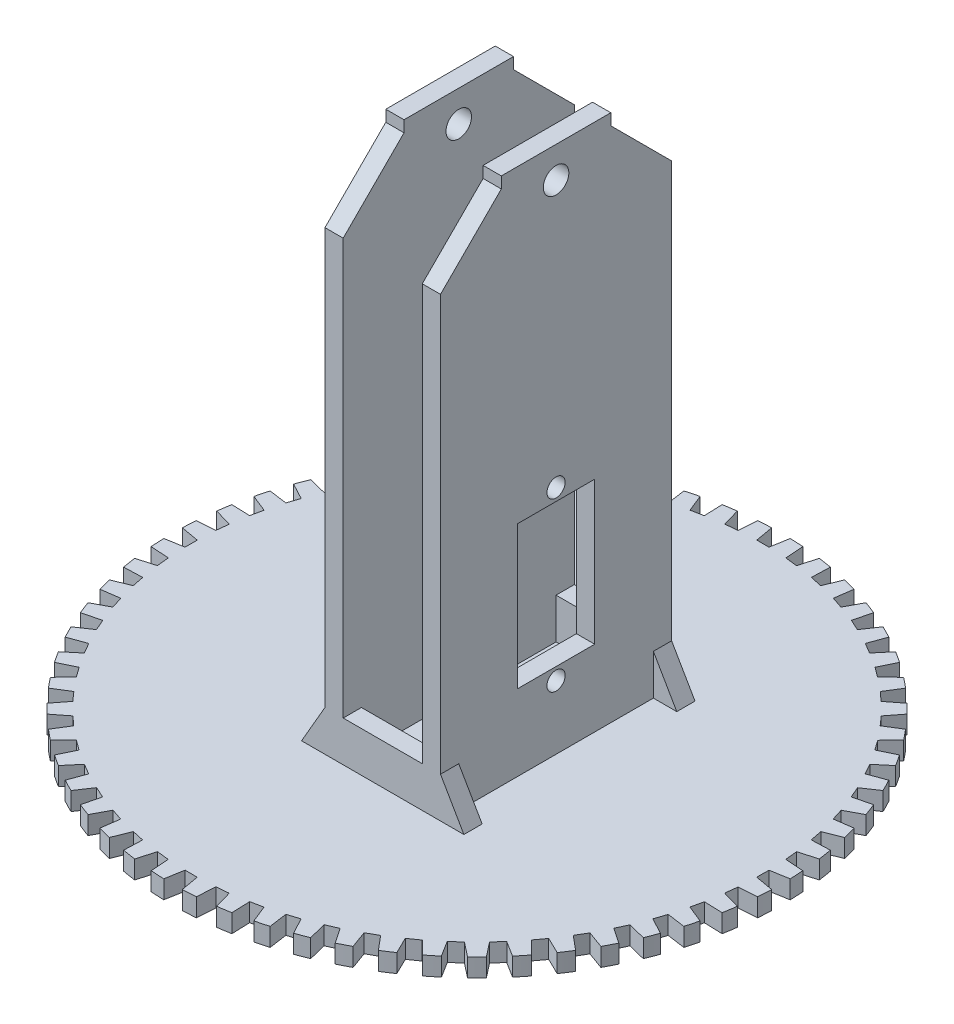
SolidWorks part; units mm, degrees
ref_plane "Спереди" through (0, 0, 0) normal (0, 0, 1) x (1, 0, 0)
ref_plane "Сверху" through (0, 0, 0) normal (0, 1, 0) x (1, 0, 0)
ref_plane "Справа" through (0, 0, 0) normal (1, 0, 0) x (0, 0, -1)
sketch "Эскиз1" plane through (0, 0, 0) normal (0, 1, 0) x (1, 0, 0)
  circle A0 centre (0, 0) radius 50
  dimension "D1" = 100
extrude "Бобышка-Вытянуть1" add sketch "Эскиз1" along normal blind 3
sketch "Эскиз2" plane through (0, 3, 0) normal (0, 1, 0) x (1, 0, 0)
  line L0 (0, 50) -> (0, 47)
  line L1 (-1, 47.0106) -> (1, 46.9894)
  line L2 (1, 46.9894) -> (1.5267, 49.9767)
  line L4 (-1, 47.0106) -> (-1.523, 49.9768)
  circle A0 centre (0, 0) radius 50 construction
  arc A1 (1, 46.9894) -> (0, 47) centre (0, 0) ccw
  arc A3 (1.5267, 49.9767) -> (-1.523, 49.9768) centre (0, 0) ccw
  point P11 (0, 47)
  dimension "D4" = 10
  dimension "D1" = 3
  dimension "D2" = 2
  dimension "D3" = 10
extrude "Вырез-Вытянуть1" cut sketch "Эскиз2" against normal blind 3 contours L1 L4 A3 L2
pattern_circular "Круговой массив1" count 60 over 360 about axis through (0, 3, 0) along (0, 1, 0) of "Вырез-Вытянуть1"
sketch "Эскиз3" plane through (0, 3, 0) normal (0, 1, 0) x (1, 0, 0)
  circle A0 centre (0, 0) radius 1.8
  dimension "D1" = 3.6
extrude "Вырез-Вытянуть2" cut sketch "Эскиз3" against normal blind 3
sketch "Эскиз4" plane through (0, 3, 0) normal (0, 1, 0) x (1, 0, 0)
  line L0 (0, -19.4939) -> (0, 19.4939) construction
  line L2 (10, -19) -> (13, -19)
  line L3 (10, -19) -> (10, 19)
  line L4 (10, 19) -> (13, 19)
  line L5 (13, -19) -> (13, 19)
  line L6 (10, -19) -> (13, 19) construction
  line L7 (10, 19) -> (13, -19) construction
  point P0 (11.5, 0)
  point P5 (0, 0)
  dimension "D1" = 3
  dimension "D2" = 38
  dimension "D3" = 0
  dimension "D4" = 13
extrude "Бобышка-Вытянуть2" add sketch "Эскиз4" along normal blind 85 contours L5 L4 L3 L2
sketch "Эскиз7" plane through (13, 0, 0) normal (1, 0, 0) x (0, 0, -1)
  line L0 (-19, 3) -> (19, 3) construction
  circle A0 centre (0, 13.5) radius 1.5
  circle A1 centre (0, 41) radius 1.5
  dimension "D1" = 3
  dimension "D2" = 3
  dimension "D3" = 27.5
  dimension "D4" = 10.5
extrude "Вырез-Вытянуть3" cut sketch "Эскиз7" against normal blind 5
sketch "Эскиз8" plane through (13, 0, 0) normal (1, 0, 0) x (0, 0, -1)
  line L0 (-19, 3) -> (19, 3) construction
  circle A0 centre (0, 84.75) radius 2.1
  dimension "D1" = 4.2
  dimension "D2" = 81.75
chamfer "Фаска1" distance 10 angle 45 2 edges at (11.5, 88, -19) (11.5, 88, 19)
sketch "Эскиз9" plane through (0, 88, 0) normal (0, 1, 0) x (1, 0, 0)
  line L1 (10, 9) -> (13, 9)
  line L2 (10, 9) -> (10, -9)
  line L3 (10, -9) -> (13, -9)
  line L4 (13, 9) -> (13, -9)
extrude "Бобышка-Вытянуть3" add sketch "Эскиз9" along normal blind 3
sketch "Эскиз10" plane through (0, 3, 0) normal (0, 1, 0) x (1, 0, 0)
  line L0 (10, -19) -> (10, 19) construction
  line L1 (-6, -19) -> (-3, -19)
  line L2 (-6, -19) -> (-6, 19)
  line L3 (-6, 19) -> (-3, 19)
  line L4 (-3, -19) -> (-3, 19)
  line L5 (-6, -19) -> (-3, 19) construction
  line L6 (-6, 19) -> (-3, -19) construction
  point P0 (-4.5, 0)
  dimension "D1" = 3
  dimension "D2" = 13
  dimension "D3" = 38
  dimension "D4" = 0
extrude "Бобышка-Вытянуть4" add sketch "Эскиз10" along normal blind 85
chamfer "Фаска2" distance 10 angle 45 2 edges at (-4.5, 88, -19) (-4.5, 88, 19)
sketch "Эскиз11" plane through (0, 88, 0) normal (0, 1, 0) x (1, 0, 0)
  line L4 (-3, -9) -> (-3, 9)
  line L5 (-3, 9) -> (-6, 9)
  line L6 (-6, 9) -> (-6, -9)
  line L7 (-6, -9) -> (-3, -9)
  line L8 (-3, -9) -> (-3, 9)
  line L9 (-3, 9) -> (-6, 9)
  line L10 (-6, 9) -> (-6, -9)
  line L11 (-6, -9) -> (-3, -9)
  dimension "D1" = 0
extrude "Бобышка-Вытянуть5" add sketch "Эскиз11" along normal blind 3
extrude "Вырез-Вытянуть5" cut sketch "Эскиз8" against normal blind 39 contours A0
sketch "Эскиз16" plane through (0, 0, 19) normal (0, 0, 1) x (1, 0, 0)
  line L0 (-6, 78) -> (-6, 3) construction
  line L1 (-6, 9.6633) -> (13, 9.6633)
  line L3 (-6, 3) -> (13, 3)
  line L5 (-6, 9.6633) -> (-9.8471, 3)
  line L6 (-9.8471, 3) -> (-6, 3)
  line L7 (3.5, 11.9442) -> (3.5, 7.3824) construction
  line L8 (16.8471, 3) -> (13, 3)
  line L9 (13, 9.6633) -> (16.8471, 3)
  point P11 (3.5, 9.6633)
  dimension "D1" = 60
extrude "Бобышка-Вытянуть6" add sketch "Эскиз16" against normal blind 3
mirror "Зеркальное отражение1" about plane through (0, 0, 0) normal (0, 0, 1) of "Бобышка-Вытянуть6"
sketch "Эскиз17" plane through (-6, 0, 0) normal (-1, 0, 0) x (0, 0, 1)
  line L0 (9, 91) -> (9, 88) construction
  line L1 (-9, 91) -> (9, 91)
  line L2 (-9, 91) -> (-9, 89.86)
  line L3 (-9, 89.86) -> (9, 89.86)
  line L4 (9, 91) -> (9, 89.86)
  dimension "D1" = 1.14
extrude "Вырез-Вытянуть6" cut sketch "Эскиз17" against normal blind 25
sketch "Эскиз18" plane through (13, 0, 0) normal (1, 0, 0) x (0, 0, -1)
  line L1 (-6.35, 15.5) -> (6.35, 15.5)
  line L2 (-6.35, 15.5) -> (-6.35, 39)
  line L3 (-6.35, 39) -> (6.35, 39)
  line L4 (6.35, 15.5) -> (6.35, 39)
  line L5 (-6.35, 15.5) -> (6.35, 39) construction
  line L6 (-6.35, 39) -> (6.35, 15.5) construction
  line L7 (19, 78) -> (19, 9.6633) construction
  circle A4 centre (0, 13.5) radius 1.5 construction
  point P0 (0, 27.25)
  point P12 (0, 27.25)
  dimension "D1" = 2
  dimension "D3" = 12.7
  dimension "D2" = 23.5
  dimension "D4" = 19
extrude "Вырез-Вытянуть7" cut sketch "Эскиз18" against normal blind 10
